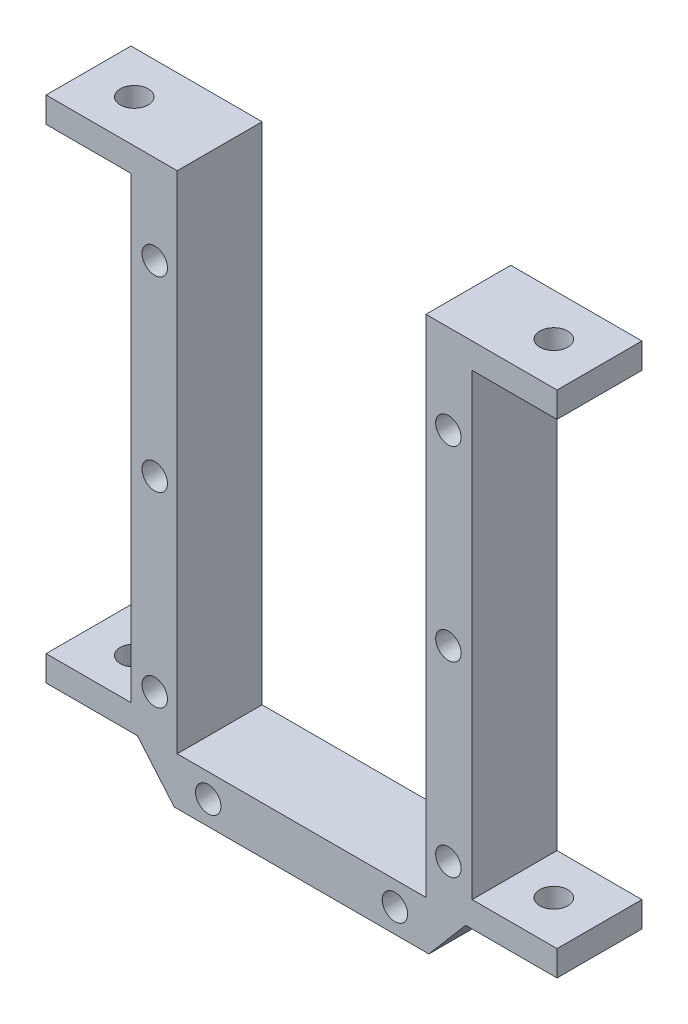
SolidWorks part; units mm, degrees
ref_plane "Front Plane" through (0, 0, 0) normal (0, 0, 1) x (1, 0, 0)
ref_plane "Top Plane" through (0, 0, 0) normal (0, 1, 0) x (1, 0, 0)
ref_plane "Right Plane" through (0, 0, 0) normal (1, 0, 0) x (0, 0, -1)
sketch "Sketch1" plane through (0, 0, 0) normal (0, 0, 1) x (1, 0, 0)
  line L1 (-20.1, 32.55) -> (20.1, 32.55)
  line L2 (-20.1, 32.55) -> (-20.1, -32.55)
  line L3 (-20.1, -32.55) -> (20.1, -32.55)
  line L4 (20.1, 32.55) -> (20.1, -32.55)
  point P0 (0, 0)
  dimension "D1" = 40.2
  dimension "D2" = 65.1
extrude "Boss-Extrude1" add sketch "Sketch1" along normal blind 10
sketch "Sketch2" plane through (0, 0, 10) normal (0, 0, 1) x (1, 0, 0)
  line L0 (0, 32.55) -> (0, -32.55) construction
  line L1 (20.1, 32.55) -> (-20.1, 32.55) construction
  line L2 (-20.1, -32.55) -> (20.1, -32.55) construction
  line L3 (-20.1, 0) -> (20.1, 0) construction
  line L4 (-20.1, 32.55) -> (-20.1, -32.55) construction
  line L5 (20.1, -32.55) -> (20.1, 32.55) construction
  line L6 (-20.1, -27.45) -> (20.1, -27.45) construction
  line L7 (15, -32.55) -> (19.335, -27.45)
  line L8 (19.335, -27.45) -> (15, -32.55) construction
  line L9 (19.335, -27.45) -> (20.1, -27.45)
  line L22 (20.1, -27.45) -> (20.1, -32.55)
  line L23 (20.1, -32.55) -> (15, -32.55)
  line L24 (-20.1, -27.45) -> (-20.1, -32.55)
  line L25 (-19.335, -27.45) -> (-20.1, -27.45)
  line L26 (-15, -32.55) -> (-19.335, -27.45)
  line L27 (-20.1, -32.55) -> (-15, -32.55)
  point P12 (0, -27.45)
  point P13 (-19.335, -27.45)
  point P17 (0, -27.45)
  point P18 (19.335, -27.45)
  dimension "D1" = 60
extrude "Cut-Extrude1" cut sketch "Sketch2" against normal blind 10
sketch "Sketch4" plane through (0, 0, 10) normal (0, 0, 1) x (1, 0, 0)
  line L0 (0, 32.55) -> (0, -32.55) construction
  line L1 (20.1, 32.55) -> (-20.1, 32.55) construction
  line L2 (-15, -32.55) -> (15, -32.55) construction
  line L3 (-20.1, 2.55) -> (20.1, 2.55) construction
  line L4 (-20.1, 32.55) -> (-20.1, -27.45) construction
  line L5 (20.1, -27.45) -> (20.1, 32.55) construction
  line L6 (14.65, -26.95) -> (-14.65, -26.95) construction
  line L7 (-14.65, -26.95) -> (-14.65, 32.55) construction
  line L8 (14.65, -26.95) -> (14.65, 32.55) construction
  line L9 (-14.65, 32.55) -> (-14.65, -26.95)
  line L10 (-14.65, -26.95) -> (14.65, -26.95)
  line L11 (14.65, -26.95) -> (14.65, 32.55)
  line L12 (14.65, 32.55) -> (-14.65, 32.55)
  point P12 (0, -26.95)
  point P16 (0, -26.95)
  dimension "D1" = 5.6
  dimension "D2" = 29.3
extrude "Cut-Extrude2" cut sketch "Sketch4" against normal blind 10
sketch "Sketch5" plane through (0, 0, 10) normal (0, 0, 1) x (1, 0, 0)
  line L0 (-14.65, 32.55) -> (14.65, 32.55) construction
  line L1 (0, 32.55) -> (0, -32.55) construction
  line L2 (-15, -32.55) -> (15, -32.55) construction
  line L3 (-15, -32.55) -> (15, -32.55) construction
  line L6 (-20.1, 32.55) -> (-20.1, -27.45) construction
  circle A0 centre (-17.3, 22.05) radius 1.5
  circle A1 centre (-17.3, 0.05) radius 1.5
  circle A2 centre (-17.3, -21.95) radius 1.5
  circle A3 centre (-11, -29.75) radius 1.5
  circle A4 centre (11, -29.75) radius 1.5
  circle A5 centre (17.3, -21.95) radius 1.5
  circle A6 centre (17.3, 0.05) radius 1.5
  circle A7 centre (17.3, 22.05) radius 1.5
  point P8 (-17.3, 22.05)
  point P9 (-17.3, 0.05)
  point P10 (-17.3, -21.95)
  point P11 (-11, -29.75)
  point P18 (0, 0)
  point P22 (11, -29.75)
  point P25 (17.3, -21.95)
  point P28 (17.3, 0.05)
  point P31 (17.3, 22.05)
  dimension "D6" = 3
  dimension "D7" = 3
  dimension "D8" = 3
  dimension "D9" = 3
  dimension "D1" = 10.6
  dimension "D2" = 32.6
  dimension "D3" = 54.6
  dimension "D4" = 2.8
  dimension "D5" = 9.1
  dimension "D10" = 17.3
  dimension "D11" = 17.3
  dimension "D12" = 17.3
extrude "Cut-Extrude3" cut sketch "Sketch5" against normal blind 10
sketch "Sketch6" plane through (0, 0, 10) normal (0, 0, 1) x (1, 0, 0)
  line L0 (-14.65, 32.55) -> (14.65, 32.55) construction
  line L1 (0, 32.55) -> (0, -32.55) construction
  line L2 (-15, -32.55) -> (15, -32.55) construction
  line L3 (-20.1, 2.55) -> (20.1, 2.55) construction
  line L4 (-20.1, 32.55) -> (-20.1, -27.45) construction
  line L5 (20.1, -27.45) -> (20.1, 32.55) construction
sketch "Sketch7" plane through (20.1, 0, 0) normal (1, 0, 0) x (0, 0, -1)
  line L0 (0, 2.55) -> (-10, 2.55) construction
  line L1 (-10, 32.55) -> (-10, -32.55) construction
  line L2 (0, -27.45) -> (0, 32.55) construction
  line L3 (0, 29.55) -> (-10, 29.55)
  line L4 (-10, 29.55) -> (-10, 32.55)
  line L5 (-10, 32.55) -> (0, 32.55)
  line L6 (0, 32.55) -> (0, 29.55)
  line L7 (-10, -27.45) -> (-10, 32.55) construction
  line L8 (-10, -27.45) -> (0, -27.45)
  line L9 (-10, -24.45) -> (-10, -27.45)
  line L10 (0, -24.45) -> (-10, -24.45)
  line L11 (0, -27.45) -> (0, -24.45)
  point P5 (0, 29.55)
  dimension "D1" = 3
extrude "Boss-Extrude2" add sketch "Sketch7" along normal blind 10
sketch "Sketch8" plane through (-20.1, 0, 0) normal (-1, 0, 0) x (0, 0, 1)
  line L0 (0, 2.55) -> (10, 2.55) construction
  line L1 (0, 32.55) -> (0, -27.45) construction
  line L2 (10, 32.55) -> (10, -32.55) construction
  line L3 (0, 29.55) -> (10, 29.55)
  line L4 (10, 29.55) -> (10, 32.55)
  line L5 (10, 32.55) -> (0, 32.55)
  line L6 (0, 32.55) -> (0, 29.55)
  line L7 (10, -27.45) -> (0, -27.45)
  line L8 (10, -24.45) -> (10, -27.45)
  line L9 (0, -24.45) -> (10, -24.45)
  line L10 (0, -27.45) -> (0, -24.45)
  point P6 (0, 29.55)
  dimension "D1" = 3
extrude "Boss-Extrude3" add sketch "Sketch8" along normal blind 10
sketch "Sketch9" plane through (0, -27.45, 0) normal (0, -1, 0) x (-1, 0, 0)
  line L0 (24.7175, -10) -> (24.7175, 0) construction
  line L1 (19.335, -10) -> (30.1, -10) construction
  line L2 (19.335, 0) -> (30.1, 0) construction
  line L3 (30.1, -5) -> (19.335, -5) construction
  line L4 (30.1, 0) -> (30.1, -10) construction
  line L5 (19.335, 0) -> (19.335, -10) construction
  circle A0 centre (24.7175, -5) radius 1.65
  dimension "D1" = 3.3
extrude "Cut-Extrude4" cut sketch "Sketch9" against normal through all
sketch "Sketch10" plane through (0, -27.45, 0) normal (0, -1, 0) x (-1, 0, 0)
  line L0 (-24.7175, -10) -> (-24.7175, 0) construction
  line L1 (-30.1, -10) -> (-19.335, -10) construction
  line L2 (-30.1, 0) -> (-19.335, 0) construction
  line L3 (-19.335, -5) -> (-30.1, -5) construction
  line L4 (-19.335, 0) -> (-19.335, -10) construction
  line L5 (-30.1, -10) -> (-30.1, 0) construction
  circle A0 centre (-24.7175, -5) radius 1.65
  dimension "D1" = 3.3
extrude "Cut-Extrude5" cut sketch "Sketch10" against normal through all
